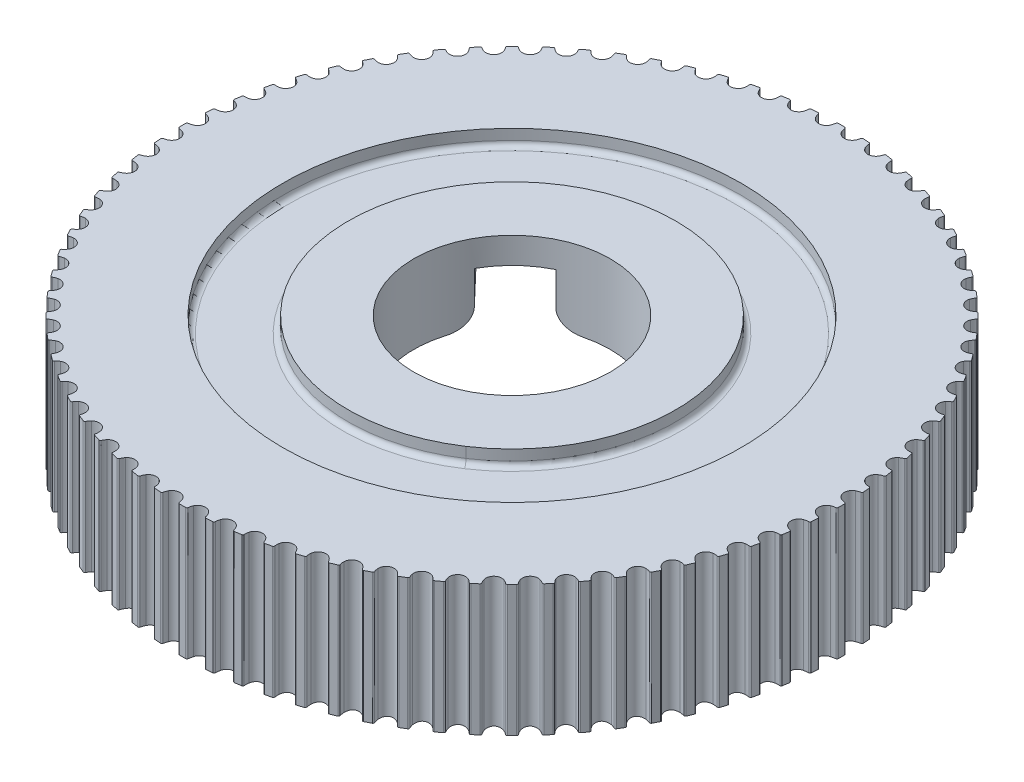
SolidWorks part; units mm, degrees
note: The reader was unsure of these and kept them because the rebuilt part matched: shared geometry of "Sketch5<4>".
ref_plane "Front Plane" through (0, 0, 0) normal (0, 0, 1) x (1, 0, 0)
ref_plane "Top Plane" through (0, 0, 0) normal (0, 1, 0) x (1, 0, 0)
ref_plane "Right Plane" through (0, 0, 0) normal (1, 0, 0) x (0, 0, -1)
ref_plane "Plane2" through (0, 10, 0) normal (0, 1, 0) x (1, 0, 0)
sketch "Sketch4" plane through (0, 10, 0) normal (0, 1, 0) x (1, 0, 0)
  line L0 (11.4658, -12.0108) -> (0, 0) construction
  line L1 (13.0571, -10.4917) -> (6.5423, -3.6672)
  line L2 (9.8745, -13.5299) -> (3.3597, -6.7054)
  line L3 (-5.0055, -4.7784) -> (5.0055, 4.7784) construction
  line L4 (-13.0571, 10.4917) -> (-6.5423, 3.6672)
  line L5 (-9.8745, 13.5299) -> (-3.3597, 6.7054)
  circle A0 centre (11.4658, -12.0108) radius 2 construction
  circle A1 centre (11.4658, -12.0108) radius 2
  arc A2 (6.5423, -3.6672) -> (-3.3597, 6.7054) centre (0, 0) ccw
  circle A3 centre (0, 0) radius 21.6
  arc A4 (9.8745, -13.5299) -> (13.0571, -10.4917) centre (11.4658, -12.0108) ccw
  circle A5 centre (11.4658, -12.0108) radius 2.2 construction
  arc A6 (-13.0571, 10.4917) -> (-9.8745, 13.5299) centre (-11.4658, 12.0108) cw
  circle A7 centre (0, 0) radius 25.215
  arc A8 (-6.5423, 3.6672) -> (3.3597, -6.7054) centre (0, 0) ccw
  dimension "D1" = 15
  dimension "D2" = 43.2
  dimension "D4" = 50.43
  dimension "D3" = 0.2
extrude "Boss-Extrude1" add sketch "Sketch4" along normal blind 4 contours A3 A8 L4 A6 L5 A2 L1 A4 L2
fillet "Fillet1" radius 1.5 6 edges at (-6.6171, 10, -10.1177) (-12.9849, 10, -13.6021) (9.7997, 10, 7.0794) (12.9849, 10, 13.6021) (-9.7997, 10, -7.0794) (6.6171, 10, 10.1177)
sketch "Sketch5" plane through (0, 14, 0) normal (0, 1, 0) x (1, 0, 0)
  circle A0 centre (0, 0) radius 21.6
  circle A1 centre (0, 0) radius 17.5
  circle A2 centre (0, 0) radius 12.5
  arc M3 (3.3597, -6.7054) -> (-6.5423, 3.6672) centre (0, 0) cw
  line M4 (-6.5423, 3.6672) -> (-13.0571, 10.4917)
  arc M5 (-13.0571, 10.4917) -> (-9.8745, 13.5299) centre (-11.4658, 12.0108) cw
  line M6 (-9.8745, 13.5299) -> (-3.3597, 6.7054)
  arc M7 (-3.3597, 6.7054) -> (6.5423, -3.6672) centre (0, 0) cw
  line M8 (6.5423, -3.6672) -> (13.0571, -10.4917)
  arc M9 (13.0571, -10.4917) -> (9.8745, -13.5299) centre (11.4658, -12.0108) cw
  line M10 (9.8745, -13.5299) -> (3.3597, -6.7054)
  dimension "D1" = 43.2
  dimension "D2" = 25
  dimension "D3" = 5
extrude "Boss-Extrude2" add sketch "Sketch5" along normal blind 2 contours A0
extrude "Cut-Extrude1" cut sketch "Sketch5<4>" against normal blind 1.2 from surface at 2 contours A2 A1 M4 M5 M9 M10 | A2 A1 M8 M9 M5 M6 | A2 A1 M10 M9 M8 | A2 A1 M6 M5 M4 | A2 M8 M6 M7 | A2 M10 M8 M7 M6 M4 M3
sketch "Sketch5<4>" plane through (0, 14, 0) normal (0, 1, 0) x (1, 0, 0) same geometry as "Sketch5"
fillet "Fillet2" radius 0.4 3 edges at (-9.0416, 14.8, 8.6313) (9.0416, 14.8, -8.6313) (0, 14.8, 17.5)
sketch "Sketch6" plane through (0, 0, 0) normal (1, 0, 0) x (0, 0, -1)
  line L0 (21.6, 16) -> (-21.6, 16) construction
  line L1 (-21.6, 10) -> (21.6, 10) construction
  line L2 (21.6, 16) -> (-21.6, 16)
  line L3 (-21.6, 10) -> (21.6, 10)
  line L4 (21.6, 16) -> (25.215, 16)
  line L5 (25.215, 16) -> (25.215, 6)
  line L6 (21.6, 10) -> (22.0241, 10)
  line L7 (25.215, 6) -> (33.1319, 6) construction
  line L8 (21.6, 16) -> (21.6, 10)
  line L9 (0, 16) -> (0, 10)
  spline S0 degree 3 poles (22.0241, 10) (22.072, 10) (23.0298, 10) (23.3389, 8.873) (23.6625, 6.7947) (24.1451, 6) (25.1641, 6) (25.215, 6) knots 0 0 0 0 0.013646 0.272929 0.716861 0.985843 1 1 1 1
  dimension "D1" = 3.615
  dimension "D2" = 10
revolve "Revolve2" add sketch "Sketch6" angle 360 about L9
sketch "Sketch8" plane through (0, 16, 0) normal (0, 1, 0) x (1, 0, 0)
  line L0 (25.469, 0) -> (25.215, 0)
  line L1 (25.4494, 0.9998) -> (25.1956, 0.9898)
  line L2 (25.4494, -0.9998) -> (25.1956, -0.9898)
  line L3 (25.1055, -1.729) -> (25.1021, -1.7788)
  line L4 (25.1021, -1.7788) -> (25.7803, -1.8269)
  line L5 (25.1638, 0.2459) -> (25.1633, 0.2959)
  line L6 (25.1633, 0.2959) -> (25.8432, 0.3039)
  arc A0 (25.1649, -1.5891) -> (25.212, -0.39) centre (0, 0) ccw
  circle A1 centre (0, 0) radius 25.469
  circle A2 centre (0, 0) radius 25.845
  arc A3 (25.1018, -2.3866) -> (25.212, -0.39) centre (25.1767, -1.3894) ccw
  arc A4 (25.0785, -0.3942) -> (25.2138, -0.2464) centre (25.0638, -0.2449) ccw
  arc A5 (25.0322, -1.5744) -> (25.1554, -1.7324) centre (25.0058, -1.7221) cw
  arc A6 (25.2117, 0.41) -> (25.1649, -1.5891) centre (25.2081, -0.59) cw
  arc A7 (25.1697, -1.5106) -> (25.2106, -0.4686) centre (24.9987, -0.9821) ccw
  circle A8 centre (25.1767, 1.3894) radius 1
  arc A9 (25.2138, 0.2464) -> (25.0785, 0.3942) centre (25.0638, 0.2449) ccw
  arc A10 (25.0322, -1.5744) -> (24.7369, -1.4721) centre (25.2081, -0.59) cw
  arc A11 (24.7762, -0.4731) -> (24.7369, -1.4721) centre (24.9987, -0.9821) ccw
  arc A12 (25.0785, -0.3942) -> (24.7762, -0.4731) centre (25.1767, -1.3894) ccw
  arc A13 (25.2138, 0.2464) -> (25.1554, -1.7324) centre (0, 0) ccw
  arc A14 (25.2138, 0.2464) -> (25.2138, -0.2464) centre (0, 0) cw
  arc A15 (25.0736, -0.3445) -> (25.1638, -0.2459) centre (25.0638, -0.2449) ccw
  arc A16 (25.0736, -0.3445) -> (24.7561, -0.4273) centre (25.1767, -1.3894) ccw
  arc A17 (24.7561, -0.4273) -> (24.7134, -1.5162) centre (24.9987, -0.9821) ccw
  arc A18 (25.0234, -1.6237) -> (24.7134, -1.5162) centre (25.2081, -0.59) cw
  arc A19 (25.0234, -1.6237) -> (25.1055, -1.729) centre (25.0058, -1.7221) cw
  arc A20 (25.1638, 0.2459) -> (25.1638, -0.2459) centre (0, 0) cw
  circle M5 centre (0, 0) radius 25.215
  dimension "D1" = 50.43
  dimension "D2" = 0.254
  dimension "D3" = 0.63
  dimension "D6" = 2
  dimension "D8" = 0.3
  dimension "D9" = 1.111
  dimension "D10" = 2
  dimension "D12" = 0.3
  dimension "D4" = 1
  dimension "D5" = 1
  dimension "D7" = 0.4
  dimension "D11" = 0.4
  dimension "D14" = 0.05
  dimension "D15" = 0.05
  dimension "D13" = 0.05
extrude "Cut-Extrude3" cut sketch "Sketch8" against normal through all contours L5 A20 A15 A16 A17 A18 A19 L3 L4 A5 A10 A11 A12 A4 A9 L6 M5 | A9 L6 M5 | L0 A1 L6 M5 | A3 A1 L0 M5 | A4 A12 A11 A10 A5 A0 M5 | A7 A1 A3 A0 | A1 A7 L2 M5 | A0 A7 A1 L2 | A7 A6 A1 M5 | A1 A6 L4 M5
pattern_circular "CirPattern2" count 80 every 4.5 about axis through (0, 0, 0) along (0, 1, 0) of "Cut-Extrude3"
sketch "Sketch9" plane through (0, 16, 0) normal (0, 1, 0) x (1, 0, 0)
  line L4 (-13.0571, 10.4917) -> (-6.5423, 3.6672)
  line L5 (-3.3597, 6.7054) -> (-9.8745, 13.5299)
  line L6 (13.0571, -10.4917) -> (6.5423, -3.6672)
  line L7 (3.3597, -6.7054) -> (9.8745, -13.5299)
  line L8 (-13.0571, 10.4917) -> (-6.5423, 3.6672)
  line L9 (-3.3597, 6.7054) -> (-9.8745, 13.5299)
  line L10 (13.0571, -10.4917) -> (6.5423, -3.6672)
  line L11 (3.3597, -6.7054) -> (9.8745, -13.5299)
  circle A0 centre (0, 0) radius 7.5
  arc A4 (-6.5423, 3.6672) -> (3.3597, -6.7054) centre (0, 0) ccw
  arc A5 (-9.8745, 13.5299) -> (-13.0571, 10.4917) centre (-11.4658, 12.0108) ccw
  arc A6 (6.5423, -3.6672) -> (-3.3597, 6.7054) centre (0, 0) ccw
  arc A7 (9.8745, -13.5299) -> (13.0571, -10.4917) centre (11.4658, -12.0108) ccw
  arc A8 (-6.5423, 3.6672) -> (3.3597, -6.7054) centre (0, 0) ccw
  arc A9 (-9.8745, 13.5299) -> (-13.0571, 10.4917) centre (-11.4658, 12.0108) ccw
  arc A10 (6.5423, -3.6672) -> (-3.3597, 6.7054) centre (0, 0) ccw
  arc A11 (9.8745, -13.5299) -> (13.0571, -10.4917) centre (11.4658, -12.0108) ccw
  dimension "D1" = 0
extrude "Cut-Extrude4" cut sketch "Sketch9" against normal through all contours A0
